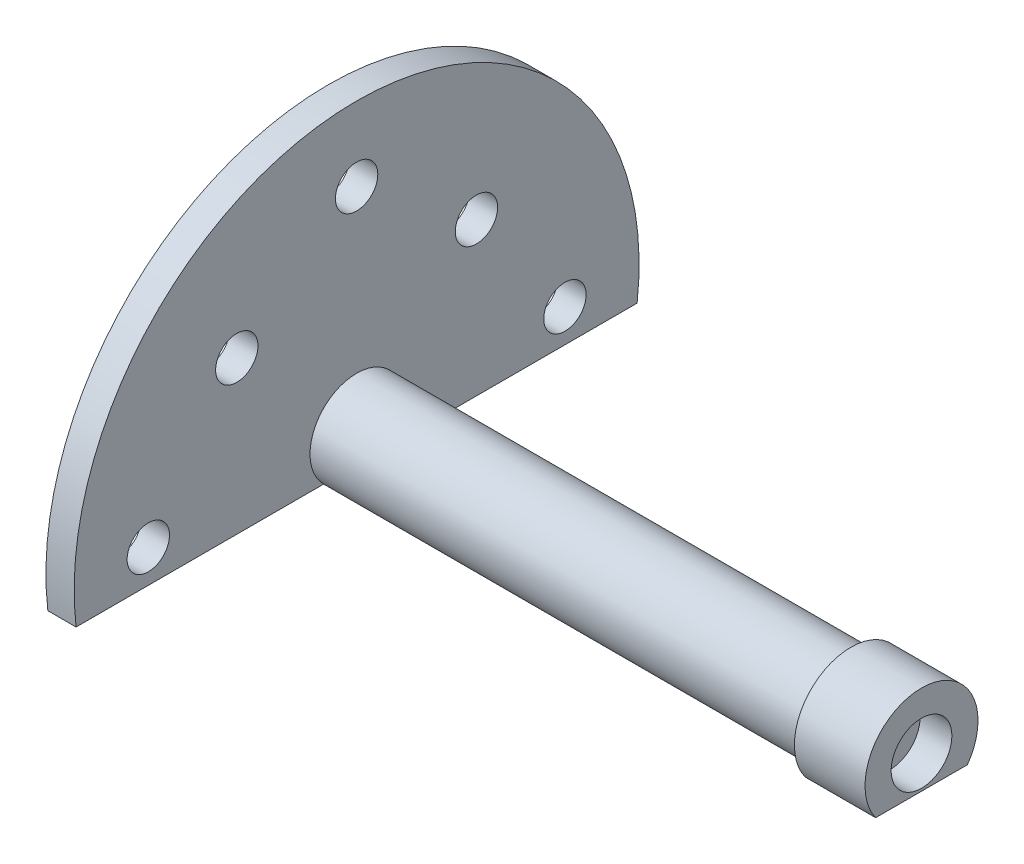
SolidWorks part; units mm, degrees
ref_plane "Front Plane" through (0, 0, 0) normal (0, 0, 1) x (1, 0, 0)
ref_plane "Top Plane" through (0, 0, 0) normal (0, 1, 0) x (1, 0, 0)
ref_plane "Right Plane" through (0, 0, 0) normal (1, 0, 0) x (0, 0, -1)
sketch "Sketch1" plane through (0, 0, 0) normal (1, 0, 0) x (0, 0, -1)
  line L0 (-8.4853, 8.4853) -> (-14.75, 0) construction
  line L1 (-8.4853, 8.4853) -> (0, 14.75) construction
  line L2 (-16.75, -2.3335) -> (-19.8634, -2.3335)
  line L3 (-16.75, -2.3335) -> (16.75, -2.3335)
  line L4 (-16.75, -2.3335) -> (-16.75, 16.75)
  line L5 (-16.75, 16.75) -> (16.75, 16.75)
  line L6 (16.75, -2.3335) -> (16.75, 16.75)
  line L7 (-2.3335, -2.3335) -> (2.3335, -2.3335)
  line L8 (-2.3335, -2.3335) -> (-2.3335, 2.3335)
  line L9 (-2.3335, 2.3335) -> (2.3335, 2.3335)
  line L10 (2.3335, -2.3335) -> (2.3335, 2.3335)
  line L11 (16.75, -2.3335) -> (19.8634, -2.3335)
  circle A0 centre (0, 0) radius 14.75 construction
  circle A1 centre (0, 14.75) radius 1.5
  circle A2 centre (0, 0) radius 14.75 construction
  circle A3 centre (14.75, 0) radius 1.5
  circle A4 centre (0, 0) radius 14.75 construction
  circle A5 centre (0, -14.75) radius 1.5 construction
  circle A6 centre (0, 0) radius 14.75 construction
  circle A7 centre (-14.75, 0) radius 1.5
  circle A8 centre (0, 0) radius 12 construction
  circle A9 centre (-8.4853, 8.4853) radius 1.5
  circle A10 centre (8.4853, 8.4853) radius 1.5
  circle A11 centre (8.4853, -8.4853) radius 1.5 construction
  circle A12 centre (-8.4853, -8.4853) radius 1.5 construction
  circle A13 centre (0, 0) radius 3.3
  circle A14 centre (0, 0) radius 20
  point P16 (0, 0)
  point P27 (0, 0)
  dimension "D1" = 4
  dimension "D2" = 4
  dimension "D3" = 2
  dimension "D6" = 3
  dimension "D7" = 6.6
  dimension "D8" = 29.5
  dimension "D9" = 24
  dimension "D10" = 40
  dimension "D4" = 2
  dimension "D5" = 2
extrude "Boss-Extrude1" add sketch "Sketch1" along normal blind 2 contours L3 L10 L9 L8 | L8 A13 | L9 A13 | L10 A13 | A13 L3 L6 L5 L4 A10 A9 A7 A3 A1 | L4 A14 L2 | L11 A14 L6 | L5 A14 region at (0, 7.246, 0) region at (0, 2.8901, 18.1289) region at (0, 0, 0) region at (0, 0, 2.7254) region at (0, 2.8901, -18.1289) region at (0, 0, -2.7254) region at (0, 2.7254, 0) region at (0, 18.0595, 0)
extrude "Boss-Extrude2" add sketch "Sketch1<3>" along normal blind 40 from surface contours L3 L10 L9 L8 | L10 A13 | L9 A13 | L8 A13 region at (0, 0, 0) region at (0, 0, 2.7254) region at (0, 0, -2.7254) region at (0, 2.7254, 0) starting at face at (2, 8.8333, 0)
sketch "Sketch1<3>" plane through (0, 0, 0) normal (1, 0, 0) x (0, 0, -1) same geometry as "Sketch1"
sketch "Sketch3" plane through (42, 0, 0) normal (1, 0, 0) x (0, 0, -1)
  circle A1 centre (0, 0) radius 2.15
extrude "Cut-Extrude1" cut sketch "Sketch3" against normal blind 2.25 contours A1
sketch "Sketch4" plane through (42, 0, 0) normal (1, 0, 0) x (0, 0, -1)
  line L0 (-3.2488, -2.3335) -> (3.2488, -2.3335)
  line L1 (-19.8634, -2.3335) -> (-2.3335, -2.3335) construction
  line L2 (2.3335, -2.3335) -> (19.8634, -2.3335) construction
  circle A0 centre (0, 0) radius 4
  circle A1 centre (0, 0) radius 2.15 construction
  circle A2 centre (0, 0) radius 2.15
  arc M2 (2.3335, -2.3335) -> (-2.3335, -2.3335) centre (0, 0) ccw
  dimension "D1" = 8
extrude "Boss-Extrude3" add sketch "Sketch4" against normal blind 5 contours L0 A0 M2 region at (42, 3.7105, 1.1944)
